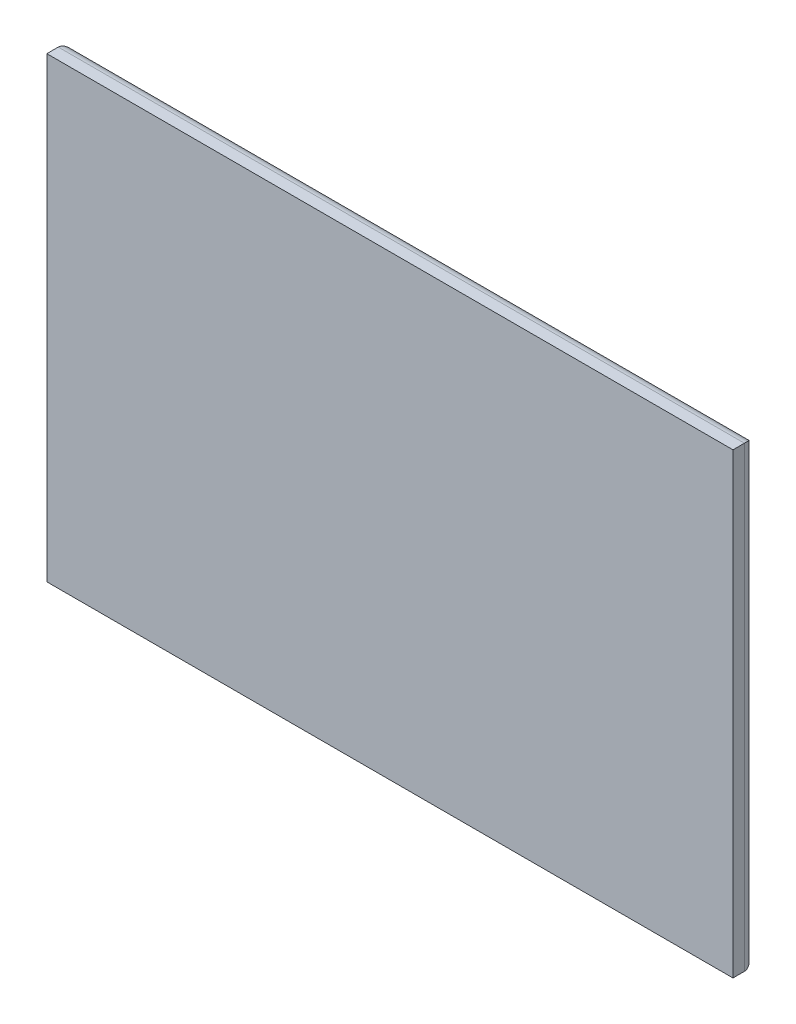
SolidWorks part; units mm, degrees
ref_plane "Front Plane" through (0, 0, 0) normal (0, 0, 1) x (1, 0, 0)
ref_plane "Top Plane" through (0, 0, 0) normal (0, 1, 0) x (1, 0, 0)
ref_plane "Right Plane" through (0, 0, 0) normal (1, 0, 0) x (0, 0, -1)
sketch "Sketch1" plane through (0, 0, 0) normal (0, 0, 1) x (1, 0, 0)
  line L0 (0, 0) -> (-25, 0) construction
  line L1 (-30, 20) -> (30, 20)
  line L2 (-30, 20) -> (-30, -20)
  line L3 (-30, -20) -> (30, -20)
  line L4 (30, 20) -> (30, -20)
  line L5 (-30, 20) -> (30, -20) construction
  line L6 (-30, -20) -> (30, 20) construction
  line L7 (-25, 0) -> (-25, 16) construction
  line L8 (-25, 0) -> (-25, -16) construction
  line L9 (0, 0) -> (25, 0) construction
  line L10 (25, 0) -> (25, 16) construction
  line L11 (25, 0) -> (25, -16) construction
  point P0 (0, 0)
extrude "Boss-Extrude1" add sketch "Sketch1" along normal blind 2
fillet "Fillet1" radius 1 4 edges at (0, 20, 0) (-30, 0, 0) (0, -20, 0) (30, 0, 0)
